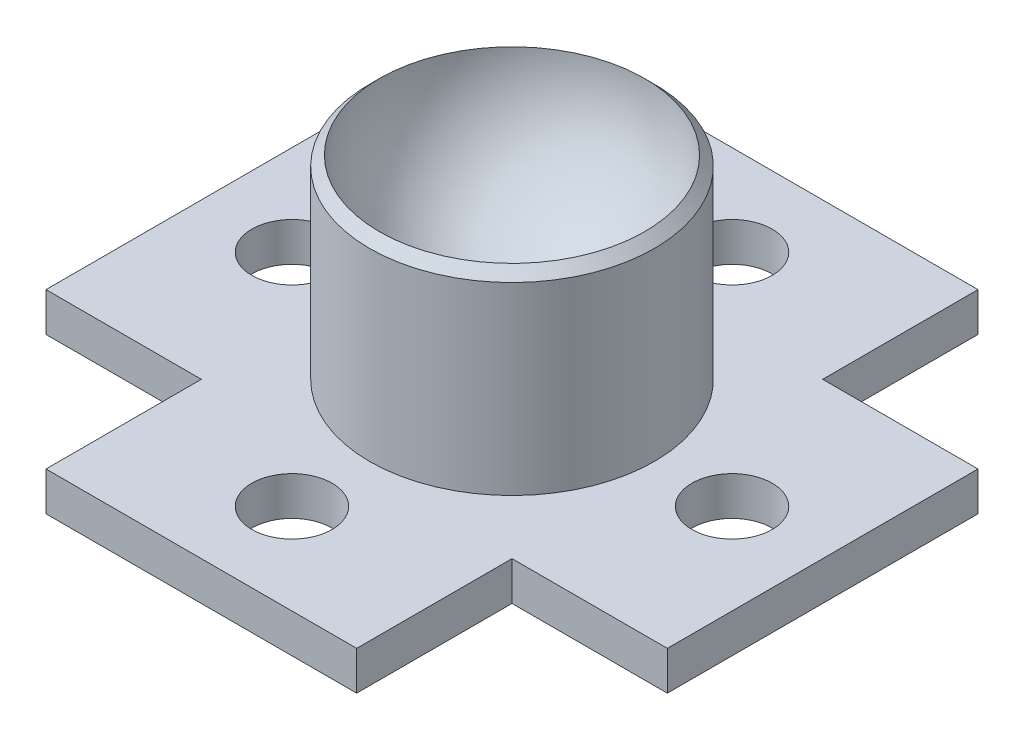
SolidWorks part; units mm, degrees
ref_plane "Front Plane" through (0, 0, 0) normal (0, 0, 1) x (1, 0, 0)
ref_plane "Top Plane" through (0, 0, 0) normal (0, 1, 0) x (1, 0, 0)
ref_plane "Right Plane" through (0, 0, 0) normal (1, 0, 0) x (0, 0, -1)
sketch "Sketch1" plane through (0, 0, 0) normal (0, 1, 0) x (1, 0, 0)
  line L0 (24, 12) -> (24, -12)
  line L1 (24, -12) -> (12, -12)
  line L2 (12, -12) -> (12, -24)
  line L3 (12, -24) -> (-12, -24)
  line L4 (0, 33.7815) -> (0, -40.437) construction
  line L5 (-42.0504, 0) -> (30.958, 0) construction
  line L6 (24, 12) -> (12, 12)
  line L7 (12, 12) -> (12, 24)
  line L8 (12, 24) -> (-12, 24)
  line L9 (-12, -12) -> (-12, -24)
  line L10 (-24, -12) -> (-12, -12)
  line L11 (-24, 12) -> (-24, -12)
  line L12 (-24, 12) -> (-12, 12)
  line L13 (-12, 12) -> (-12, 24)
  circle A0 centre (17, 0) radius 3.1
  circle A1 centre (0, -17) radius 3.1
  circle A2 centre (0, 17) radius 3.1
  circle A3 centre (-17, 0) radius 3.1
  circle A4 centre (0, 0) radius 11
  point P20 (24, 0)
  point P24 (0, -24)
  point P29 (0, 24)
  dimension "D4" = 3.1
  dimension "D5" = 7
  dimension "D6" = 3.1
  dimension "D7" = 22
  dimension "D1" = 48
  dimension "D2" = 24
  dimension "D3" = 7
extrude "Boss-Extrude1" add sketch "Sketch1" along normal blind 3 contours A3 | A2 | A0 | A1 | L10 L9 L3 L2 L1 L0 L6 L7 L8 L13 L12 L11 region at (17, 0, 0) region at (0, 0, 17) region at (0, 0, -17) region at (-17, 0, 0)
extrude "Boss-Extrude2" add sketch "Sketch1<5>" along normal blind 15 from surface contours A4 starting at face at (-17, 3, 3.1)
sketch "Sketch1<5>" plane through (0, 0, 0) normal (0, 1, 0) x (1, 0, 0) same geometry as "Sketch1"
sketch "Sketch3" plane through (0, 0, 0) normal (0, 0, 1) x (1, 0, 0)
  line L0 (12, 0) -> (-12, 0) construction
  line L1 (0, 18) -> (10.25, 18)
  line L2 (0, 18) -> (0, -2.2179) construction
  line L3 (0, 18) -> (0, 7.75)
  arc A0 (0, 7.75) -> (10.25, 18) centre (0, 18) ccw
  dimension "D1" = 10.25
  dimension "D2" = 7.75
revolve "Cut-Revolve3" cut sketch "Sketch3" angle 360 about L2
chamfer "Chamfer1" distance 0.75 angle 45 1 edges at (0, 18, 11)
